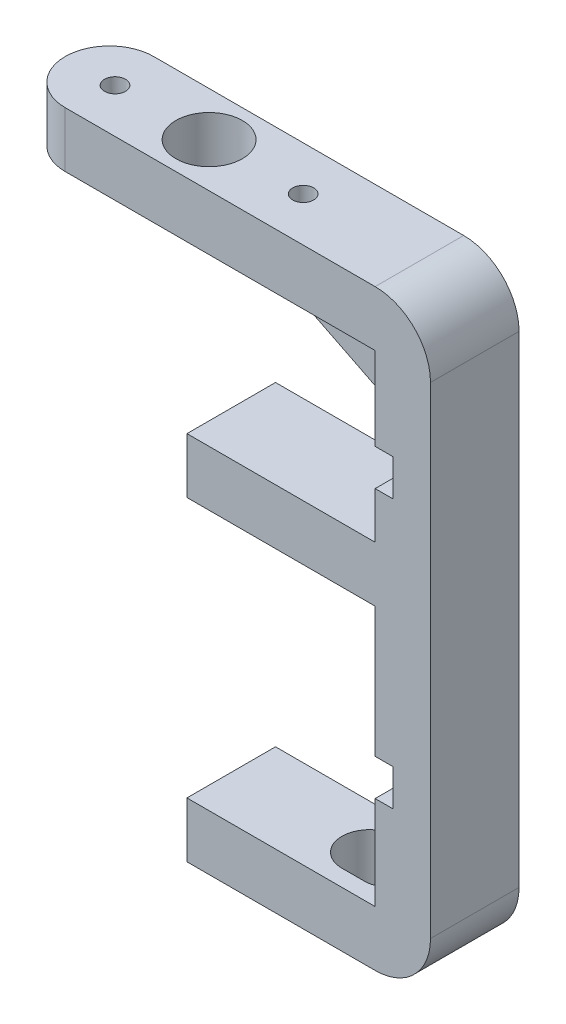
SolidWorks part; units mm, degrees
material "ABS"
ref_plane "Přední rovina" through (0, 0, 0) normal (0, 0, 1) x (1, 0, 0)
ref_plane "Horní rovina" through (0, 0, 0) normal (0, 1, 0) x (1, 0, 0)
ref_plane "Pravá rovina" through (0, 0, 0) normal (1, 0, 0) x (0, 0, -1)
sketch "Skica1" plane through (0, 0, 0) normal (0, 0, 1) x (1, 0, 0)
  line L0 (0, 0) -> (17, 0)
  line L1 (17, 0) -> (17, 23.5)
  line L2 (17, 23.5) -> (0, 23.5)
  line L3 (0, 23.5) -> (0, 28.5)
  line L4 (0, 28.5) -> (22, 28.5)
  line L5 (22, 28.5) -> (22, -5)
  line L6 (22, -5) -> (0, -5)
  line L7 (0, -5) -> (0, 0)
  dimension "D1" = 23.5
  dimension "D2" = 17
  dimension "D3" = 5
  dimension "D4" = 5
extrude "Přidat vysunutím1" add sketch "Skica1" along normal mid plane 8
sketch "Skica2" plane through (0, 28.5, 0) normal (0, 1, 0) x (1, 0, 0)
  line L0 (22, -4) -> (0, -4) construction
  line L1 (22, 4) -> (17, 4)
  line L2 (22, 4) -> (22, -4)
  line L3 (22, -4) -> (17, -4)
  line L4 (17, 4) -> (17, -4)
  dimension "D1" = 5
extrude "Přidat vysunutím2" add sketch "Skica2" along normal blind 20
sketch "Skica3" plane through (17, 0, 0) normal (-1, 0, 0) x (0, 0, 1)
  line L0 (-4, 48.5) -> (-4, 28.5) construction
  line L1 (4, 48.5) -> (-4, 48.5)
  line L2 (4, 48.5) -> (4, 43.5)
  line L3 (4, 43.5) -> (-4, 43.5)
  line L4 (-4, 48.5) -> (-4, 43.5)
  dimension "D1" = 5
extrude "Přidat vysunutím3" add sketch "Skica3" along normal blind 32
sketch "Skica4" plane through (0, 0, 0) normal (0, 0, 1) x (1, 0, 0)
  line L0 (17, 43.5) -> (7, 43.5)
  line L1 (-15, 43.5) -> (17, 43.5) construction
  line L2 (7, 43.5) -> (17, 38.5)
  line L3 (17, 43.5) -> (17, 28.5) construction
  line L4 (17, 38.5) -> (17, 43.5)
  dimension "D1" = 5
  dimension "D2" = 10
extrude "Přidat vysunutím4" add sketch "Skica4" along normal mid plane 5
sketch "Skica5" plane through (0, 48.5, 0) normal (0, 1, 0) x (1, 0, 0)
  line L0 (-15, 0) -> (-2, 0) construction
  line L1 (-15, -4) -> (-15, 4) construction
  circle A0 centre (-2, 0) radius 3
  dimension "D1" = 6
  dimension "D2" = 13
extrude "Odebrat vysunutím1" cut sketch "Skica5" against normal blind 15
fillet "Zaoblit1" radius 5 2 edges at (22, -5, 0) (22, 48.5, 0)
sketch "Skica6" plane through (0, 0, 0) normal (-1, 0, 0) x (0, 0, 1)
  circle A0 centre (-0.0001, 25.0937) radius 1.2
  circle A1 centre (-0.0001, -1.8938) radius 1.2
  dimension "D1" = 2.4
extrude "Odebrat vysunutím2" cut sketch "Skica6" against normal blind 8
fillet "Zaoblit2" radius 4 2 edges at (-15, 46, -4) (-15, 46, 4)
sketch "Skica7" plane through (0, 48.5, 0) normal (0, 1, 0) x (1, 0, 0)
  line L0 (-10.5, 0) -> (6.5, 0) construction
  line L1 (6.5, 0) -> (0, 0) construction
  circle A0 centre (-10.5, 0) radius 0.95
  circle A1 centre (6.5, 0) radius 0.95
  circle A2 centre (-2, 0) radius 3 construction
  dimension "D1" = 1.9
  dimension "D2" = 17
  dimension "D3" = 8.5
extrude "Odebrat vysunutím3" cut sketch "Skica7" against normal blind 13
sketch "Skica8" plane through (0, 0, 0) normal (0, 1, 0) x (1, 0, 0)
  line L0 (0, 0) -> (22.7268, 0) construction
  line L1 (12.5, 0) -> (14.5, 0) construction
  line L2 (12.5, 2.5) -> (14.5, 2.5)
  line L3 (12.5, -2.5) -> (14.5, -2.5)
  line L4 (17, -4) -> (17, 4) construction
  arc A0 (12.5, 2.5) -> (12.5, -2.5) centre (12.5, 0) ccw
  arc A1 (14.5, -2.5) -> (14.5, 2.5) centre (14.5, 0) ccw
  point P5 (13.5, 0)
  point P10 (17, 0)
  dimension "D1" = 5
  dimension "D2" = 2
extrude "Odebrat vysunutím4" cut sketch "Skica8" against normal blind 10
sketch "Skica9" plane through (0, 0, 4) normal (0, 0, 1) x (1, 0, 0)
  line L0 (17, 43.5) -> (17, 28.5) construction
  line L1 (17, 36) -> (18.6, 36)
  line L2 (17, 36) -> (17, 32.7)
  line L3 (17, 32.7) -> (18.6, 32.7)
  line L4 (18.6, 36) -> (18.6, 32.7)
  line L5 (17, 23.5) -> (17, 0) construction
  line L6 (17, 11.75) -> (18.6, 11.75)
  line L7 (17, 11.75) -> (17, 8.45)
  line L8 (17, 8.45) -> (18.6, 8.45)
  line L9 (18.6, 11.75) -> (18.6, 8.45)
  line L10 (17, 28.5) -> (0, 28.5) construction
  line L11 (17, 0) -> (0, 0) construction
  dimension "D1" = 3.3
  dimension "D2" = 1.6
  dimension "D3" = 4.2
  dimension "D4" = 8.45
extrude "Odebrat vysunutím5" cut sketch "Skica9" against normal blind 10
equation "\"D3@Skica7\"=\"D2@Skica7\"/2"
